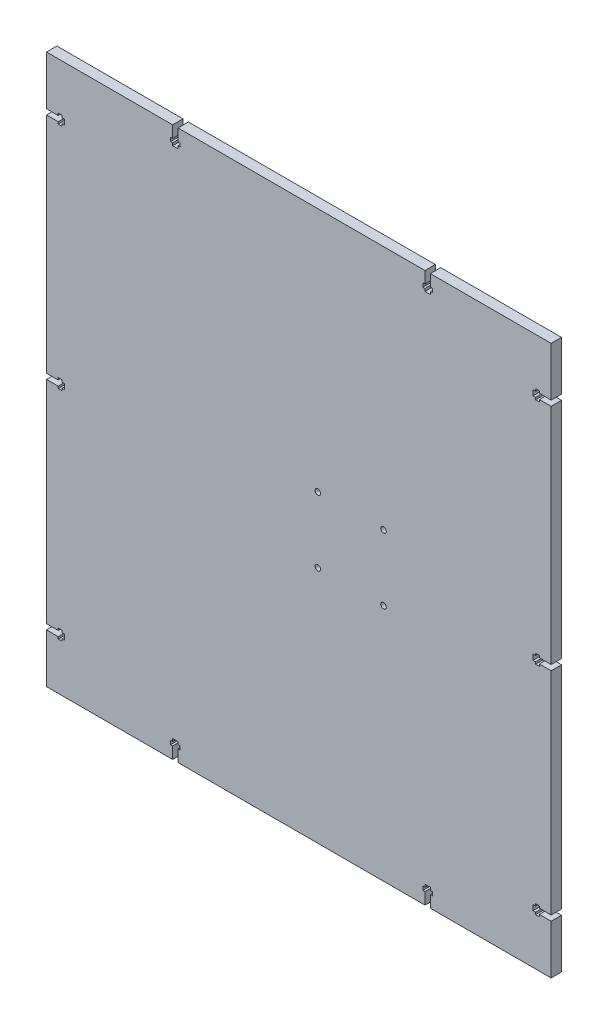
SolidWorks part; units mm, degrees
material "Клен"
ref_plane "Спереди" through (0, 0, 0) normal (0, 0, 1) x (1, 0, 0)
ref_plane "Сверху" through (0, 0, 0) normal (0, 1, 0) x (1, 0, 0)
ref_plane "Справа" through (0, 0, 0) normal (1, 0, 0) x (0, 0, -1)
sketch "Эскиз1" plane through (0, 0, 0) normal (0, 0, 1) x (1, 0, 0)
  line L0 (-142.6276, 165.1762) -> (-69.6276, 165.1762)
  line L5 (-142.6276, 165.1762) -> (-142.6276, 136.7262)
  line L6 (-142.6276, -152.8238) -> (-69.6276, -152.8238)
  line L7 (149.3724, 165.1762) -> (149.3724, 136.7262)
  line L8 (3.3724, 203.8374) -> (3.3724, -203.8374) construction
  line L9 (196.2616, 4.2262) -> (-196.2616, 4.2262) construction
  line L10 (-191.5634, 135.1762) -> (196.2616, 135.1762) construction
  line L11 (-191.5634, -124.3738) -> (186.5064, -124.3738) construction
  line L12 (-142.6276, -124.3738) -> (-142.6276, -152.8238)
  line L13 (-69.6276, 203.8374) -> (-69.6276, -203.8374) construction
  line L14 (76.3724, 203.8374) -> (76.3724, -203.8374) construction
  line L15 (-66.5276, 165.1762) -> (76.3724, 165.1762)
  line L16 (79.4724, 165.1762) -> (149.3724, 165.1762)
  line L17 (-66.5276, -152.8238) -> (76.3724, -152.8238)
  line L18 (79.4724, -152.8238) -> (149.3724, -152.8238)
  line L19 (196.2616, 136.7262) -> (-191.5634, 136.7262) construction
  line L20 (142.5724, 136.7262) -> (142.5724, 137.9262)
  line L21 (140.3724, 132.4262) -> (142.5724, 132.4262)
  line L22 (140.3724, 136.7262) -> (138.8724, 136.7262)
  line L23 (142.5724, 137.9262) -> (140.3724, 137.9262)
  line L24 (149.3724, 136.7262) -> (142.5724, 136.7262)
  line L25 (138.8724, 133.6262) -> (140.3724, 133.6262)
  line L26 (79.4724, 158.3762) -> (79.4724, 165.1762)
  line L27 (79.4724, 156.1762) -> (80.6724, 156.1762)
  line L28 (76.3724, 154.6762) -> (79.4724, 154.6762)
  line L29 (79.4724, 154.6762) -> (79.4724, 156.1762)
  line L30 (76.3724, 165.1762) -> (76.3724, 158.3762)
  line L31 (76.3724, 158.3762) -> (75.1724, 158.3762)
  line L32 (80.6724, 156.1762) -> (80.6724, 158.3762)
  line L33 (75.1724, 158.3762) -> (75.1724, 156.1762)
  line L34 (80.6724, 158.3762) -> (79.4724, 158.3762)
  line L35 (75.1724, 156.1762) -> (76.3724, 156.1762)
  line L36 (76.3724, 156.1762) -> (76.3724, 154.6762)
  line L37 (-66.5276, 158.3762) -> (-66.5276, 165.1762)
  line L38 (-66.5276, 156.1762) -> (-65.3276, 156.1762)
  line L39 (-69.6276, 154.6762) -> (-66.5276, 154.6762)
  line L40 (-66.5276, 154.6762) -> (-66.5276, 156.1762)
  line L41 (-69.6276, 165.1762) -> (-69.6276, 158.3762)
  line L42 (-69.6276, 158.3762) -> (-70.8276, 158.3762)
  line L43 (-65.3276, 156.1762) -> (-65.3276, 158.3762)
  line L44 (-70.8276, 158.3762) -> (-70.8276, 156.1762)
  line L45 (-65.3276, 158.3762) -> (-66.5276, 158.3762)
  line L46 (-70.8276, 156.1762) -> (-69.6276, 156.1762)
  line L47 (-69.6276, 156.1762) -> (-69.6276, 154.6762)
  line L48 (-69.6276, -143.8238) -> (-69.6276, -142.3238)
  line L49 (-70.8276, -143.8238) -> (-69.6276, -143.8238)
  line L50 (-65.3276, -146.0238) -> (-66.5276, -146.0238)
  line L51 (-70.8276, -146.0238) -> (-70.8276, -143.8238)
  line L52 (-65.3276, -143.8238) -> (-65.3276, -146.0238)
  line L53 (-69.6276, -146.0238) -> (-70.8276, -146.0238)
  line L54 (-69.6276, -152.8238) -> (-69.6276, -146.0238)
  line L55 (-66.5276, -142.3238) -> (-66.5276, -143.8238)
  line L56 (-69.6276, -142.3238) -> (-66.5276, -142.3238)
  line L57 (-66.5276, -143.8238) -> (-65.3276, -143.8238)
  line L58 (-66.5276, -146.0238) -> (-66.5276, -152.8238)
  line L59 (76.3724, -143.8238) -> (76.3724, -142.3238)
  line L60 (75.1724, -143.8238) -> (76.3724, -143.8238)
  line L61 (80.6724, -146.0238) -> (79.4724, -146.0238)
  line L62 (75.1724, -146.0238) -> (75.1724, -143.8238)
  line L63 (80.6724, -143.8238) -> (80.6724, -146.0238)
  line L64 (76.3724, -146.0238) -> (75.1724, -146.0238)
  line L65 (76.3724, -152.8238) -> (76.3724, -146.0238)
  line L66 (79.4724, -142.3238) -> (79.4724, -143.8238)
  line L67 (76.3724, -142.3238) -> (79.4724, -142.3238)
  line L68 (79.4724, -143.8238) -> (80.6724, -143.8238)
  line L69 (79.4724, -146.0238) -> (79.4724, -152.8238)
  line L70 (142.5724, 132.4262) -> (142.5724, 133.6262)
  line L71 (142.5724, 133.6262) -> (149.3724, 133.6262)
  line L72 (138.8724, 136.7262) -> (138.8724, 133.6262)
  line L73 (140.3724, 137.9262) -> (140.3724, 136.7262)
  line L74 (140.3724, 133.6262) -> (140.3724, 132.4262)
  line L75 (149.3724, 132.0762) -> (149.3724, 133.6262)
  line L76 (142.5724, -121.2738) -> (142.5724, -120.0738)
  line L77 (142.5724, -124.3738) -> (149.3724, -124.3738)
  line L78 (138.8724, -121.2738) -> (138.8724, -124.3738)
  line L79 (140.3724, -120.0738) -> (140.3724, -121.2738)
  line L80 (140.3724, -121.2738) -> (138.8724, -121.2738)
  line L81 (138.8724, -124.3738) -> (140.3724, -124.3738)
  line L82 (149.3724, -121.2738) -> (142.5724, -121.2738)
  line L83 (142.5724, -120.0738) -> (140.3724, -120.0738)
  line L84 (140.3724, -124.3738) -> (140.3724, -125.5738)
  line L85 (140.3724, -125.5738) -> (142.5724, -125.5738)
  line L86 (142.5724, -125.5738) -> (142.5724, -124.3738)
  line L87 (149.3724, -124.3738) -> (149.3724, -152.8238)
  line L88 (-133.6276, 133.6262) -> (-133.6276, 132.4262)
  line L89 (-133.6276, 137.9262) -> (-133.6276, 136.7262)
  line L90 (-132.1276, 136.7262) -> (-132.1276, 133.6262)
  line L91 (-135.8276, 133.6262) -> (-142.6276, 133.6262)
  line L92 (-135.8276, 132.4262) -> (-135.8276, 133.6262)
  line L93 (-132.1276, 133.6262) -> (-133.6276, 133.6262)
  line L94 (-142.6276, 136.7262) -> (-135.8276, 136.7262)
  line L95 (-135.8276, 137.9262) -> (-133.6276, 137.9262)
  line L96 (-133.6276, 136.7262) -> (-132.1276, 136.7262)
  line L97 (-133.6276, 132.4262) -> (-135.8276, 132.4262)
  line L98 (-135.8276, 136.7262) -> (-135.8276, 137.9262)
  line L99 (-135.8276, -125.5738) -> (-135.8276, -124.3738)
  line L100 (-133.6276, -125.5738) -> (-135.8276, -125.5738)
  line L101 (-133.6276, -124.3738) -> (-133.6276, -125.5738)
  line L102 (-135.8276, -120.0738) -> (-133.6276, -120.0738)
  line L103 (-142.6276, -121.2738) -> (-135.8276, -121.2738)
  line L104 (-132.1276, -124.3738) -> (-133.6276, -124.3738)
  line L105 (-133.6276, -121.2738) -> (-132.1276, -121.2738)
  line L106 (-133.6276, -120.0738) -> (-133.6276, -121.2738)
  line L107 (-132.1276, -121.2738) -> (-132.1276, -124.3738)
  line L108 (-135.8276, -124.3738) -> (-142.6276, -124.3738)
  line L109 (-135.8276, -121.2738) -> (-135.8276, -120.0738)
  line L110 (149.3724, 132.0762) -> (149.3724, 4.2262)
  line L111 (138.8724, 4.2262) -> (138.8724, 1.1262)
  line L112 (138.8724, 1.1262) -> (140.3724, 1.1262)
  line L113 (140.3724, 4.2262) -> (138.8724, 4.2262)
  line L114 (142.5724, 1.1262) -> (149.3724, 1.1262)
  line L115 (140.3724, -0.0738) -> (142.5724, -0.0738)
  line L116 (142.5724, -0.0738) -> (142.5724, 1.1262)
  line L117 (142.5724, 5.4262) -> (140.3724, 5.4262)
  line L118 (140.3724, 5.4262) -> (140.3724, 4.2262)
  line L119 (149.3724, 4.2262) -> (142.5724, 4.2262)
  line L120 (142.5724, 4.2262) -> (142.5724, 5.4262)
  line L121 (140.3724, 1.1262) -> (140.3724, -0.0738)
  line L122 (149.3724, 1.1262) -> (149.3724, -121.2738)
  line L123 (-133.6276, 1.1262) -> (-133.6276, -0.0738)
  line L124 (-135.8276, 4.2262) -> (-135.8276, 5.4262)
  line L125 (-142.6276, 4.2262) -> (-135.8276, 4.2262)
  line L126 (-133.6276, 5.4262) -> (-133.6276, 4.2262)
  line L127 (-135.8276, 5.4262) -> (-133.6276, 5.4262)
  line L128 (-135.8276, -0.0738) -> (-135.8276, 1.1262)
  line L129 (-133.6276, -0.0738) -> (-135.8276, -0.0738)
  line L130 (-135.8276, 1.1262) -> (-142.6276, 1.1262)
  line L131 (-133.6276, 4.2262) -> (-132.1276, 4.2262)
  line L132 (-132.1276, 1.1262) -> (-133.6276, 1.1262)
  line L133 (-132.1276, 4.2262) -> (-132.1276, 1.1262)
  line L134 (-142.6276, 133.6262) -> (-142.6276, 4.2262)
  line L135 (-142.6276, -121.2738) -> (-142.6276, 1.1262)
  line L136 (-31.5144, 23.2262) -> (33.277, 23.2262) construction
  line L137 (22.3724, 48.9126) -> (22.3724, 13.4316) construction
  line L138 (-45.6276, 68.2193) -> (-45.6276, -33.0401) construction
  line L139 (52.3724, 68.2193) -> (52.3724, -33.0401) construction
  circle A8 centre (14.3724, -14.7738) radius 1.6
  circle A9 centre (52.3724, 23.2262) radius 1.6
  circle A10 centre (14.3724, 23.2262) radius 1.6
  circle A11 centre (52.3724, -14.7738) radius 1.6
  dimension "D9" = 97
  dimension "D1" = 292
  dimension "D2" = 318
  dimension "D3" = 30
  dimension "D4" = 73
  dimension "D5" = 73
  dimension "D6" = 28.45
  dimension "D7" = 28.45
  dimension "D8" = 160.95
extrude "Бобышка-Вытянуть1" add sketch "Эскиз1" along normal blind 6
